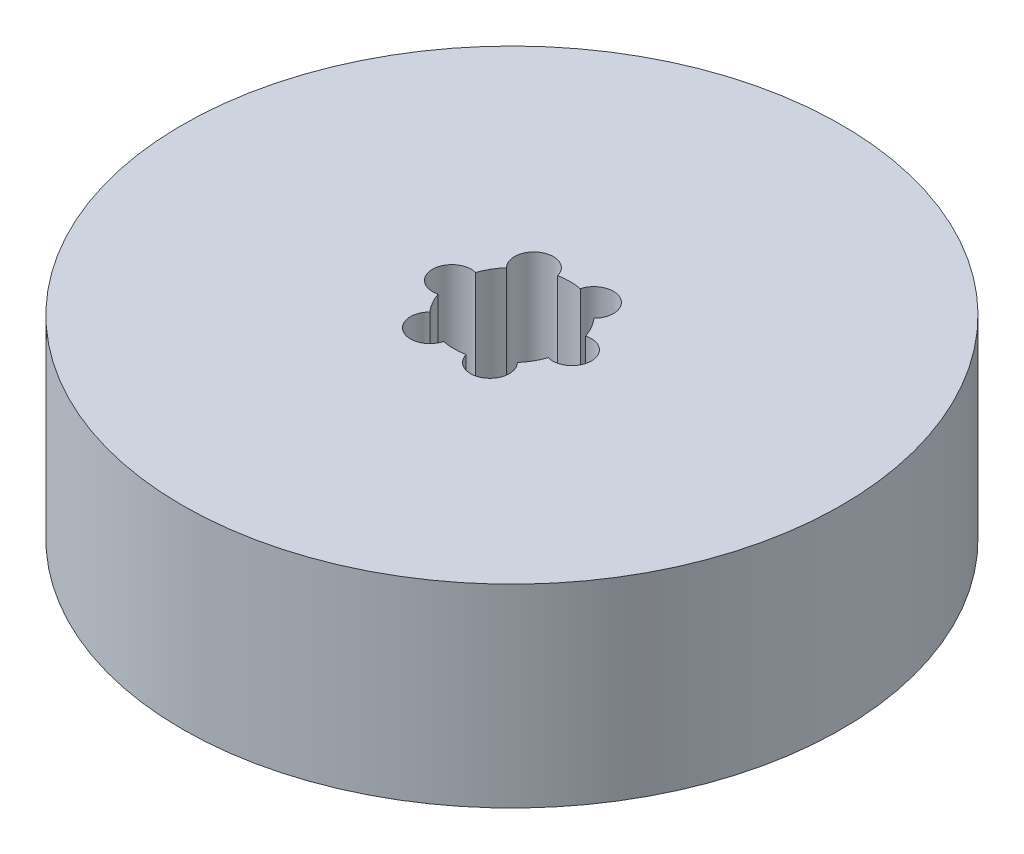
SolidWorks part; units mm, degrees
ref_plane "Front Plane" through (0, 0, 0) normal (0, 0, 1) x (1, 0, 0)
ref_plane "Top Plane" through (0, 0, 0) normal (0, 1, 0) x (1, 0, 0)
ref_plane "Right Plane" through (0, 0, 0) normal (1, 0, 0) x (0, 0, -1)
sketch "Sketch1" plane through (0, 0, 0) normal (0, 1, 0) x (1, 0, 0)
  circle A0 centre (0, 0) radius 42.5
  dimension "FLANGE_OD" = 85
extrude "Boss-Extrude1" add sketch "Sketch1" along normal blind 25
sketch "Sketch2" plane through (0, 0, 0) normal (0, 1, 0) x (1, 0, 0)
  circle A0 centre (0, 0) radius 7.5
  dimension "BORE_D" = 15
extrude "Cut-Extrude1" cut sketch "Sketch2" along normal through all
sketch "Sketch3" plane through (0, 25, 0) normal (0, 1, 0) x (1, 0, 0)
  circle A0 centre (0, 0) radius 7.7463 construction
  circle A1 centre (-7.7463, 0) radius 2.5007
  dimension "BOLT_D" = 5.0014
  dimension "BOLT_PCD" = 15.4927
extrude "Cut-Extrude2" cut sketch "Sketch3" against normal blind 16.1748
pattern_circular "CirPattern1" count 6 over 360 about axis through (0, 0, 0) along (0, 1, 0) of "Cut-Extrude2"
